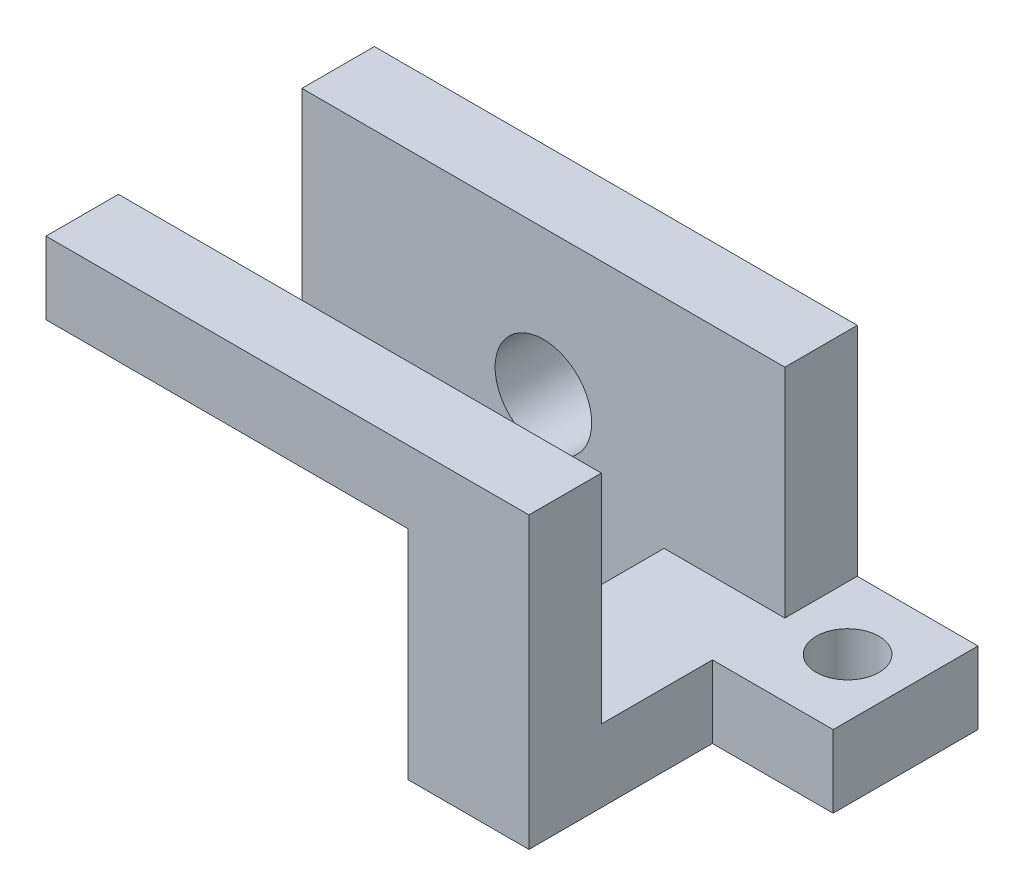
SolidWorks part; units mm, degrees
ref_plane "Front Plane" through (0, 0, 0) normal (0, 0, 1) x (1, 0, 0)
ref_plane "Top Plane" through (0, 0, 0) normal (0, 1, 0) x (1, 0, 0)
ref_plane "Right Plane" through (0, 0, 0) normal (1, 0, 0) x (0, 0, -1)
sketch "Sketch1" plane through (0, 0, 0) normal (0, 1, 0) x (1, 0, 0)
  line L0 (-55, 0) -> (55, 0) construction
  line L1 (-50, 0) -> (50, 0)
  line L2 (-50, 0) -> (-50, 15)
  line L3 (-50, 15) -> (50, 15)
  line L4 (50, 0) -> (50, 15)
  line L5 (25, -38) -> (25, -53)
  line L6 (50, 15) -> (75, 15)
  line L7 (50, 15) -> (50, -15)
  line L8 (50, -15) -> (75, -15)
  line L9 (75, 15) -> (75, -15)
  line L10 (50, 0) -> (25, 0)
  line L11 (50, 0) -> (50, -38)
  line L12 (50, -38) -> (25, -38)
  line L13 (25, 0) -> (25, -38)
  line L14 (50, -38) -> (-50, -38)
  line L15 (50, -38) -> (50, -53)
  line L16 (50, -53) -> (-50, -53)
  line L17 (-50, -38) -> (-50, -53)
  circle A0 centre (63, 0) radius 6.5
  dimension "D10" = 13
  dimension "D1" = 100
  dimension "D2" = 50
  dimension "D3" = 15
  dimension "D4" = 30
  dimension "D5" = 50
  dimension "D6" = 25
  dimension "D7" = 100
  dimension "D8" = 15
  dimension "D9" = 23
  dimension "D11" = 12
  dimension "D12" = 15
extrude "Boss-Extrude1" add sketch "Sketch1" along normal blind 60 contours L1 L4 L3 L2 region at (0, 0, -7.5)
extrude "Boss-Extrude2" add sketch "Sketch1<6>" along normal blind 15 contours L16 L15 L12 L5 | L1 L13 L12 L11 L7 | L9 L6 L4 L7 L8 region at (37.5, 0, 19) region at (50.3905, 0, -7.5) region at (37.5, 0, 45.5)
sketch "Sketch1<6>" plane through (0, 0, 0) normal (0, 1, 0) x (1, 0, 0) same geometry as "Sketch1"
extrude "Boss-Extrude3" add sketch "Sketch1<7>" along normal blind 60 contours L16 L15 L12 L5 region at (37.5, 0, 45.5)
sketch "Sketch1<7>" plane through (0, 0, 0) normal (0, 1, 0) x (1, 0, 0) same geometry as "Sketch1"
extrude "Boss-Extrude4" add sketch "Sketch1<8>" against normal blind 15 from surface contours L14 L17 L16 L5 region at (-12.5, 0, 45.5) starting at face at (37.5, 60, 45.5)
sketch "Sketch1<8>" plane through (0, 0, 0) normal (0, 1, 0) x (1, 0, 0) same geometry as "Sketch1"
sketch "Sketch2" plane through (0, 0, 0) normal (0, 0, 1) x (1, 0, 0)
  line L0 (-50, 60) -> (-50, 0) construction
  line L1 (50, 60) -> (-50, 60) construction
  circle A0 centre (0, 30) radius 10
  dimension "D3" = 20
  dimension "D1" = 50
  dimension "D2" = 30
extrude "Cut-Extrude1" cut sketch "Sketch2" against normal blind 15
